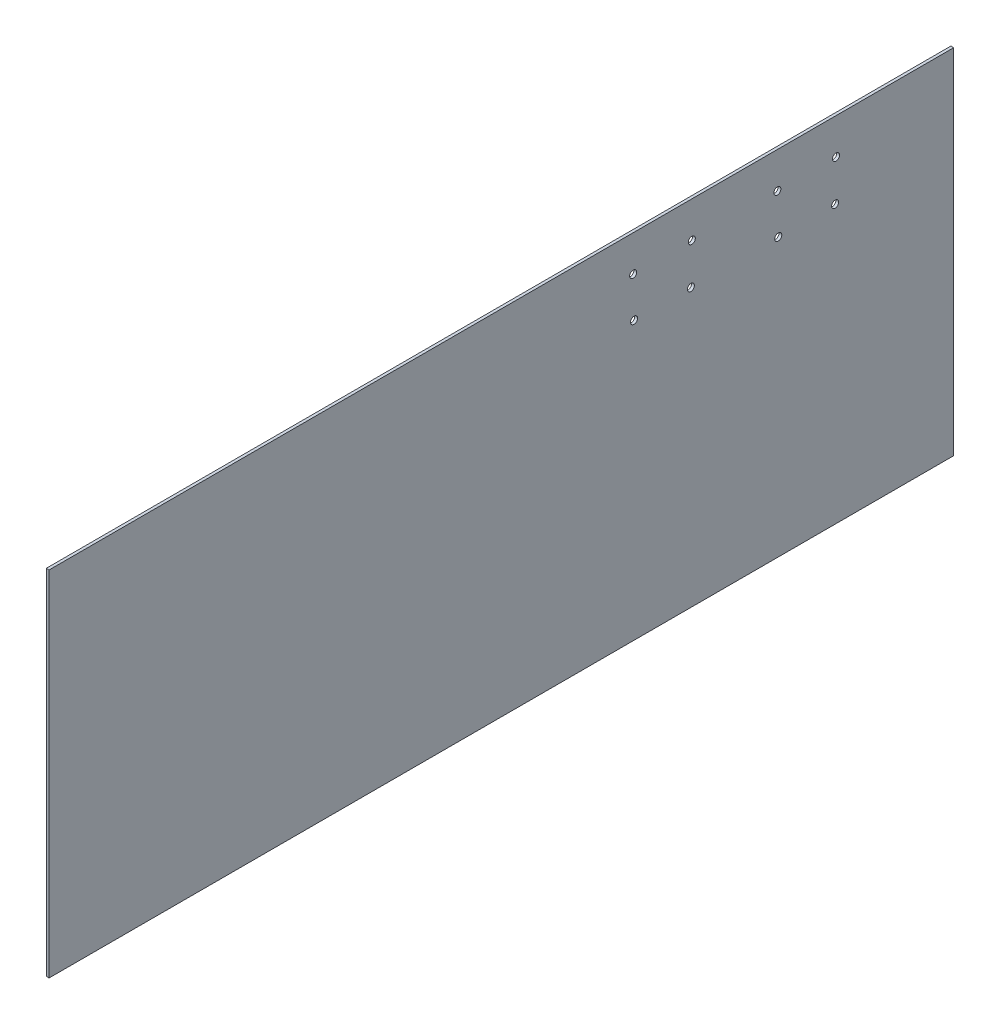
SolidWorks part; units mm, degrees
ref_plane "Front Plane" through (0, 0, 0) normal (0, 0, 1) x (1, 0, 0)
ref_plane "Top Plane" through (0, 0, 0) normal (0, 1, 0) x (1, 0, 0)
ref_plane "Right Plane" through (0, 0, 0) normal (1, 0, 0) x (0, 0, -1)
sketch "Sketch1" plane through (0, 0, 0) normal (1, 0, 0) x (0, 0, -1)
  line L0 (1.2451, 135.7198) -> (1.2451, -114.2802) construction
  line L1 (-318.7549, 135.7198) -> (321.2451, 135.7198)
  line L2 (-318.7549, 135.7198) -> (-318.7549, -114.2802)
  line L3 (-318.7549, -114.2802) -> (321.2451, -114.2802)
  line L4 (321.2451, 135.7198) -> (321.2451, -114.2802)
  line L5 (-158.7549, 10.7198) -> (161.2451, 10.7198) construction
  line L6 (-158.7549, 10.7198) -> (-158.7549, 135.7198) construction
  line L8 (161.2451, 10.7198) -> (161.2451, 135.7198) construction
  circle A0 centre (94.4453, 110.3182) radius 2.5
  circle A1 centre (135.9363, 110.3182) radius 2.5
  circle A2 centre (95.0728, 81.7782) radius 2.5
  circle A3 centre (135.2895, 81.7782) radius 2.5
  circle A4 centre (196.4723, 110.3182) radius 2.5
  circle A5 centre (197.0998, 81.7782) radius 2.5
  circle A6 centre (237.3165, 81.7782) radius 2.5
  circle A7 centre (237.9634, 110.3182) radius 2.5
  circle A8 centre (-158.7549, 10.7198) radius 28.0033 construction
  circle A9 centre (161.2451, 10.7198) radius 25.1308 construction
  dimension "D1" = 640
  dimension "D2" = 250
extrude "Boss-Extrude1" add sketch "Sketch1" along normal blind 2
